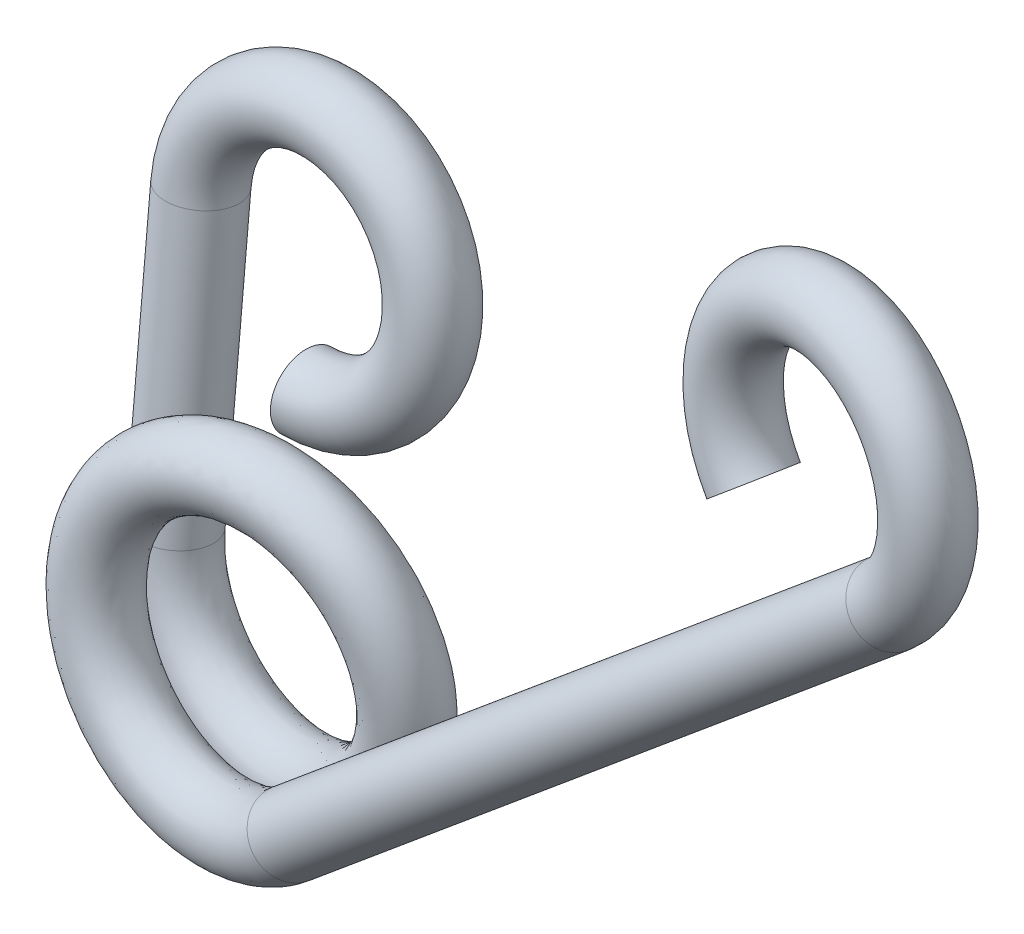
SolidWorks part; units mm, degrees
note: '?' marks a value the reader was unsure of.
ref_plane "Front Plane" through (0, 0, 0) normal (0, 0, 1) x (1, 0, 0)
ref_plane "Top Plane" through (0, 0, 0) normal (0, 1, 0) x (1, 0, 0)
ref_plane "Right Plane" through (0, 0, 0) normal (1, 0, 0) x (0, 0, -1)
sketch "Sketch1" plane through (0, 0, 0) normal (0, 0, 1) x (1, 0, 0)
  circle A0 centre (0, 0) radius 2.925
  dimension "D1" = 5.85
curve "Helix/Spiral1" pitch 1.6911 height 2.304 radius 2.925 centre (0, 0, 0) axis (0, 0, 1) start towards (1, 0, 0)
sweep "Sweep1" add path "Helix/Spiral1" circular profile diameter 1.537 parameters "D3"=1.537
sketch "Sketch7" plane through (0, 0, 0) normal (0, 0.9958, -0.0916) x (1, 0, 0)
  line L0 (-3.6935, 0) -> (-2.1565, 0) construction
  circle A0 centre (-2.925, 0) radius 0.7685 construction
  circle A1 centre (-2.925, 0) radius 0.7685
extrude "Boss-Extrude1" add sketch "Sketch7" along normal blind 6.112
sketch "Sketch8" plane through (0.1599, 0.1365, 0.0193) normal (0.7575, 0.6464, 0.0916) x (0.1475, -0.0327, -0.9885)
  line L0 (-1.9252, -3.9489) -> (-1.9252, -2.4119) construction
  circle A0 centre (-1.9252, -3.1804) radius 0.7685 construction
  circle A1 centre (-1.9252, -3.1804) radius 0.7685
extrude "Boss-Extrude2" add sketch "Sketch8" along normal blind 19.442
ref_axis "Axis1" through (-2.925, 6.0352, -0.5553) along (0, -0.9958, 0.0916)?
ref_plane "Plane1" through (0, 0, 0) normal (0, 0.0916, 0.9958) x (1, 0, 0)
ref_axis "Axis2" through (17.2539, 10.878, 4.1617) along (-0.7575, -0.6464, -0.0916)?
ref_plane "Plane2" through (-0.2839, 0.0629, 1.9031) normal (0.1475, -0.0327, -0.9885) x (-0.9891, -0.0035, -0.1474)
sketch "Sketch10" plane through (0, 0, 0) normal (0, 0.0916, 0.9958) x (1, 0, 0)
  line L0 (-2.1565, 6.112) -> (-3.6935, 6.112) construction
  line L1 (-2.1565, 6.112) -> (-3.6935, 6.112) construction
  line L2 (-2.925, 6.0607) -> (-2.925, 0.0513) construction
  line L3 (-2.925, 6.112) -> (-0.425, 6.112) construction
  line L5 (-0.425, 6.112) -> (-0.425, 3.612) construction
  arc A0 (-2.925, 6.112) -> (-0.425, 3.612) centre (-0.425, 6.112) cw
  dimension "D2" = 2.5
  dimension "D1" = 90
sketch "Sketch11" plane through (0, 6.0863, -0.56) normal (0, 0.9958, -0.0916) x (1, 0, 0)
  circle A0 centre (-2.925, 0) radius 0.7685 construction
  circle A1 centre (-2.925, 0) radius 0.7685
sweep "Sweep2" add profiles "Sketch11" path "Sketch10"
sketch "Sketch12" plane through (-0.2839, 0.0629, 1.9031) normal (0.1475, -0.0327, -0.9885) x (-0.9891, -0.0035, -0.1474)
  line L0 (-16.5879, 10.8123) -> (-17.5778, 9.6365) construction
  line L1 (-16.5879, 10.8123) -> (-17.5778, 9.6365) construction
  line L2 (-17.7172, 10.7584) -> (-1.5588, -2.8451) construction
  line L3 (-17.0828, 10.2244) -> (-15.4727, 12.1369) construction
  line L5 (-15.4727, 12.1369) -> (-13.5603, 10.5268) construction
  arc A0 (-17.0828, 10.2244) -> (-13.5603, 10.5268) centre (-15.4727, 12.1369) cw
  dimension "D2" = 2.5
  dimension "D1" = 90
sketch "Sketch13" plane through (14.8871, 12.7035, 1.8008) normal (0.7575, 0.6464, 0.0916) x (0.1475, -0.0327, -0.9885)
  circle A0 centre (-1.9252, -3.1804) radius 0.7685 construction
  circle A1 centre (-1.9252, -3.1804) radius 0.7685
sweep "Sweep3" add profiles "Sketch13" path "Sketch12"
equation "\"D_coil\"=0.005850"
equation "\"d_wire\"=0.001537"
equation "\"Nb\"=1.362432"
equation "\"loop_diam\"=0.005000"
equation "\"height\"=0.002304"
equation "\"D1@Sketch1\"=\"D_coil\"*1000"
equation "\"D3@Helix/Spiral1\"=\"height\"*1000"
equation "\"D5@Helix/Spiral1\"=\"Nb\""
equation "\"D3@Sweep1\"=\"d_wire\"*1000"
equation "\"D1@Boss-Extrude1\" = \"l_s_arm\" * 1000"
equation "\"D1@Boss-Extrude2\"= \"l_a_arm\" * 1000"
equation "\"D2@Sketch10\"=\"loop_diam\"*1000/2"
equation "\"D2@Sketch12\"=\"loop_diam\"*1000/2"
equation "\"l_s_arm\"=0.006112"
equation "\"l_a_arm\"=0.019442"
